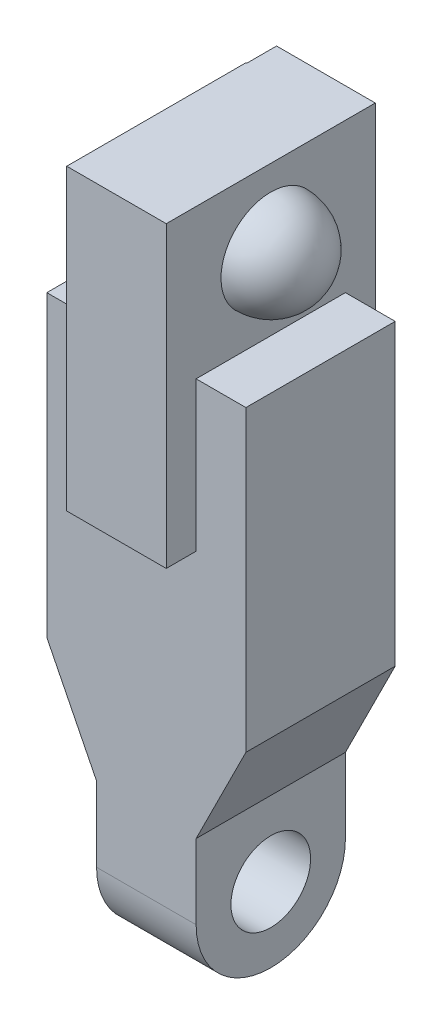
SolidWorks part; units mm, degrees
ref_plane "Front Plane" through (0, 0, 0) normal (0, 0, 1) x (1, 0, 0)
ref_plane "Top Plane" through (0, 0, 0) normal (0, 1, 0) x (1, 0, 0)
ref_plane "Right Plane" through (0, 0, 0) normal (1, 0, 0) x (0, 0, -1)
sketch "Sketch1" plane through (0, 0, 0) normal (0, 0, 1) x (1, 0, 0)
  line L1 (-4.878, 6.0772) -> (5.122, 6.0772)
  line L2 (-4.878, 6.0772) -> (-4.878, -23.9228)
  line L3 (-4.878, -23.9228) -> (5.122, -23.9228)
  line L4 (5.122, 6.0772) -> (5.122, -23.9228)
  dimension "D1" = 10
  dimension "D2" = 30
extrude "Boss-Extrude1" add sketch "Sketch1" along normal blind 15 contours L2 L1 L4 L3
sketch "Sketch2" plane through (0, 0, 15) normal (0, 0, 1) x (1, 0, 0)
  line L0 (-9.878, -8.9228) -> (-4.878, -8.9228)
  line L1 (-4.878, -48.9228) -> (-9.878, -38.9228)
  line L2 (-4.878, 6.0772) -> (-4.878, -23.9228) construction
  line L4 (-9.878, -8.9228) -> (-9.878, -38.9228)
  line L6 (10.122, -8.9228) -> (10.122, -38.9228)
  line L7 (-4.878, -8.9228) -> (-4.878, -23.9228)
  line L8 (-4.878, -23.9228) -> (5.122, -23.9228)
  line L9 (5.122, -23.9228) -> (5.122, -8.9228)
  line L10 (5.122, 6.0772) -> (5.122, -23.9228) construction
  line L11 (5.122, -8.9228) -> (10.122, -8.9228)
  line L13 (-4.878, -48.9228) -> (5.122, -48.9228)
  line L15 (5.122, -48.9228) -> (10.122, -38.9228)
  dimension "D1" = 5
  dimension "D2" = 5
  dimension "D3" = 30
sketch "Sketch3" plane through (0, 0, 15) normal (0, 0, 1) x (1, 0, 0)
extrude "Boss-Extrude5" add sketch "Sketch2" against normal blind 15 contours L13 L15 L6 L11 L2 L0 L4 L1 | L1 L4 L0 L7 L8 L9 L11 L6 L15 L13 region at (0.122, -30.6589, 15)
sketch "Sketch5" plane through (0, 0, 15) normal (0, 0, 1) x (1, 0, 0)
sketch "Sketch6" plane through (0, 0, 15) normal (0, 0, 1) x (1, 0, 0)
  line L1 (-4.878, 6.0772) -> (5.122, 6.0772)
  line L2 (-4.878, 6.0772) -> (-4.878, -23.9228)
  line L3 (-4.878, -23.9228) -> (5.122, -23.9228)
  line L4 (5.122, 6.0772) -> (5.122, -23.9228)
  dimension "D1" = 30
extrude "Boss-Extrude6" add sketch "Sketch6" along normal blind 3
sketch "Sketch7" plane through (0, 0, 0) normal (0, 0, -1) x (-1, 0, 0)
  line L3 (-5.122, 6.0772) -> (4.7948, 6.0772)
  line L4 (-5.122, 6.0772) -> (-5.122, -23.9228)
  line L5 (-5.122, -23.9228) -> (4.7948, -23.9228)
  line L6 (4.7948, 6.0772) -> (4.7948, -23.9228)
  dimension "D1" = 30
extrude "Boss-Extrude7" add sketch "Sketch7" along normal blind 3
sketch "Sketch9" plane through (0, 6.0772, 0) normal (0, 1, 0) x (1, 0, 0)
  line L1 (-4.7948, 3) -> (5.122, 3)
  line L2 (-4.7948, 3) -> (-4.7948, -18)
  line L3 (-4.7948, -18) -> (5.122, -18)
  line L4 (5.122, 3) -> (5.122, -18)
sketch "Sketch10" plane through (-4.878, 0, 0) normal (-1, 0, 0) x (0, 0, 1)
  line L1 (7.5, 3.5772) -> (7.5, -6.4228)
  arc A1 (7.5, 3.5772) -> (7.5, -6.4228) centre (7.5, -1.4228) ccw
sketch "Sketch11" plane through (0, 0, 15) normal (0, 0, 1) x (1, 0, 0)
sketch "Sketch12" plane through (0, -48.9228, 0) normal (0, -1, 0) x (1, 0, 0)
  line L1 (-4.878, 15) -> (5.122, 15)
  line L2 (-4.878, 15) -> (-4.878, 0)
  line L3 (-4.878, 0) -> (5.122, 0)
  line L4 (5.122, 15) -> (5.122, 0)
extrude "Boss-Extrude9" add sketch "Sketch12" along normal blind 15
sketch "Sketch13" plane through (-4.878, 0, 0) normal (-1, 0, 0) x (0, 0, 1)
  circle A0 centre (7.5, -56.4228) radius 4
  dimension "D1" = 8
extrude "Cut-Extrude3" cut sketch "Sketch13" against normal blind 15
fillet "Fillet2" radius 7.5 2 edges at (0.122, -63.9228, 0) (0.122, -63.9228, 15)
sketch "Sketch15" plane through (5.122, 0, 0) normal (1, 0, 0) x (0, 0, -1)
  line L0 (-7.5, 3.5772) -> (-7.5, -6.4228)
  arc A0 (-7.5, 3.5772) -> (-7.5, -6.4228) centre (-7.5, -1.4228) ccw
  dimension "D1" = 10
revolve "Cut-Revolve1" cut sketch "Sketch10" angle 360 about L1
revolve "Revolve1" add sketch "Sketch15" angle 360 about L0
